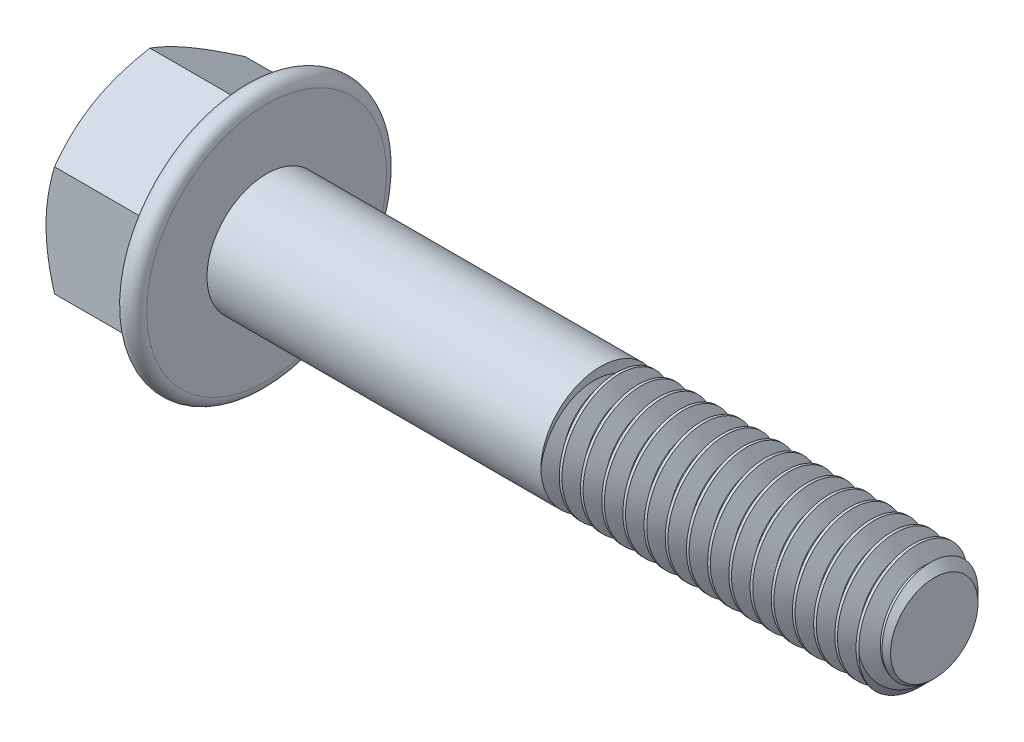
SolidWorks part; units mm, degrees
ref_plane "Front Plane" through (0, 0, 0) normal (0, 0, 1) x (1, 0, 0)
ref_plane "Top Plane" through (0, 0, 0) normal (0, 1, 0) x (1, 0, 0)
ref_plane "Right Plane" through (0, 0, 0) normal (1, 0, 0) x (0, 0, -1)
sketch "Sketch1" plane through (0, 0, 0) normal (0, 0, 1) x (1, 0, 0)
  line L0 (0, 0) -> (44.45, 0) construction
  line L1 (0, 0) -> (-8.3344, 0) construction
  line L2 (0, 8.7312) -> (0, -8.7312) construction
  line L3 (-8.3344, 6.35) -> (-8.3344, -6.35) construction
  line L4 (44.45, 3.9688) -> (44.45, -3.9688) construction
  point P8 (22.225, 0)
  point P11 (39.5111, -3.9688)
  dimension "D1" = 4.9389
sketch "Sketch2" plane through (0, 0, 0) normal (1, 0, 0) x (0, 0, -1)
  circle A0 centre (0, 0) radius 3.9688
extrude "Boss-Extrude1" add sketch "Sketch2" along normal up to vertex (44.45 mm away) up to point (44.45, 3.9688, 0)
chamfer "Chamfer1" distance 1.0583 angle 45 1 edges at (44.45, 0, -3.9688)
sketch "Sketch12" plane through (44.45, 0, 0) normal (1, 0, 0) x (0, 0, -1)
  circle A0 centre (0, 0) radius 3.9688 construction
  circle A1 centre (0, 0) radius 3.9688
curve "Helix/Spiral2" pitch 1.4111 height 45.8611 radius 3.9688 centre (44.45, 0, 0) axis (-1, 0, 0) start towards (0, 1, 0) parameters "Pitch"=1.4111
sketch "Sketch13" plane through (0, 0, 0) normal (0, 0, 1) x (1, 0, 0)
  line L0 (44.45, 3.9688) -> (44.9792, 3.0522)
  line L1 (44.9792, 3.0522) -> (45.1556, 3.0522)
  line L2 (45.1556, 3.0522) -> (45.6847, 3.9688)
  line L3 (45.6847, 3.9688) -> (44.45, 3.9688)
  line L4 (45.0674, 3.9688) -> (45.0674, 3.0522) construction
  line L5 (44.7146, 3.5105) -> (45.4201, 3.5105) construction
  line L6 (44.45, -3.9688) -> (44.45, 3.9688) construction
  dimension "D1" = 60
  dimension "D2" = 0.7056
  dimension "D3" = 0.1764
sweep "Cut-Sweep1" cut profiles "Sketch13" path "Helix/Spiral2" align with end faces yes
ref_plane "Plane1" through (22.225, 0, 0) normal (1, 0, 0) x (0, 0, -1)
sketch "Sketch3" plane through (0, 0, 0) normal (-1, 0, 0) x (0, 0, 1)
  line L0 (0, 7.3323) -> (0, 0) construction
  line L1 (0, 7.3323) -> (-6.35, 3.6662)
  line L2 (-6.35, 3.6662) -> (-6.35, -3.6662)
  line L3 (-6.35, -3.6662) -> (0, -7.3323)
  line L4 (0, -7.3323) -> (6.35, -3.6662)
  line L5 (6.35, -3.6662) -> (6.35, 3.6662)
  line L6 (6.35, 3.6662) -> (0, 7.3323)
  circle A0 centre (0, 0) radius 6.35 construction
extrude "Boss-Extrude2" add sketch "Sketch3" along normal up to vertex (8.3344 mm away) up to point (-8.3344, 6.35, 0)
sketch "Sketch4" plane through (0, 0, 0) normal (0, 0, 1) x (1, 0, 0)
  line L0 (0, 0) -> (0, 7.9869)
  line L1 (-0.7444, 8.7312) -> (0, 8.7312) construction
  line L2 (-1.3891, 8.3591) -> (-2.549, 6.35)
  line L3 (-2.549, 6.35) -> (-2.549, 0)
  line L4 (0, 0) -> (-8.3344, 0) construction
  line L5 (-2.549, 0) -> (0, 0)
  line L6 (-8.3344, 6.35) -> (-2.549, 6.35) construction
  arc A0 (0, 7.9869) -> (-1.3891, 8.3591) centre (-0.7444, 7.9869) ccw
  dimension "D1" = 30
  dimension "D2" = 1.3891
revolve "Revolve1" add sketch "Sketch4" angle 360 about L5
sketch "Sketch5" plane through (-8.3344, 0, 0) normal (-1, 0, 0) x (0, 0, 1)
  circle A0 centre (0, 0) radius 6.35 construction
  circle A1 centre (0, 0) radius 6.35
extrude "Cut-Extrude1" cut sketch "Sketch5" against normal up to vertex (8.3344 mm away) draft 60 flip side to cut up to point (0, 0, 0)
sketch "Sketch6" plane through (-8.3344, 0, 0) normal (-1, 0, 0) x (0, 0, 1)
  line L0 (0, 6.35) -> (0, -6.35) construction
  circle A0 centre (0, 0) radius 5.715
  dimension "D1" = 11.43
extrude "Cut-Extrude2" cut sketch "Sketch6" against normal blind 0.6945 draft 35
sketch "Sketch11" plane through (-7.6398, 0, 0) normal (-1, 0, 0) x (0, 0, 1)
  line L0 (0, 4.8895) -> (0, 1.7145) construction
  line L1 (0.1905, 4.8895) -> (0.1905, 1.7145)
  line L2 (-0.1905, 4.8895) -> (-0.1905, 1.7145)
  arc A0 (0.1905, 4.8895) -> (-0.1905, 4.8895) centre (0, 4.8895) ccw
  arc A1 (-0.1905, 1.7145) -> (0.1905, 1.7145) centre (0, 1.7145) ccw
  circle A2 centre (0, 0) radius 5.08 construction
  circle A3 centre (0, 0) radius 1.524 construction
  point P3 (0, 3.302)
  dimension "D1" = 10.16
  dimension "D2" = 3.048
  dimension "D3" = 0.381
extrude "Cut-Extrude3" cut sketch "Sketch11" against normal blind 0.254
pattern_circular "CirPattern1" count 6 over 360 about axis through (0, 0, 0) along (1, 0, 0) of "Cut-Extrude3"
sketch "Sketch14" plane through (0, 0, 0) normal (0, 0, 1) x (1, 0, 0)
  line L0 (0, 3.9687) -> (0, 0)
  line L1 (0, 0) -> (22.225, 0)
  line L2 (22.225, 0) -> (22.225, 3.9687)
  line L3 (22.225, 3.9687) -> (0, 3.9687)
revolve "Revolve2" add sketch "Sketch14" angle 360 mid plane about L1
equation "\"D2@Sketch4\" = \"Head Ht.@Sketch1\" / 6"
equation "\"D1@Sketch6\" = \"Head Wd.@Sketch1\" * 0.9"
equation "\"D1@Cut-Extrude2\" = \"D2@Sketch4\" / 2"
equation "\"D1@Sketch11\" = \"Head Wd.@Sketch1\"*.8"
equation "\"D2@Sketch11\" = \"D1@Sketch11\"*.3"
equation "\"D3@Sketch11\" = \"Head Wd.@Sketch1\"*.03"
equation "\"D2@Sketch13\" = \"Pitch@Helix/Spiral2\"*.50"
equation "\"D3@Sketch13\" = \"Pitch@Helix/Spiral2\"*.125"
equation "\"D3@Helix/Spiral2\" = \"Lg.@Sketch1\"+\"Pitch@Helix/Spiral2\""
equation "\"D1@Chamfer1\" = \"Pitch@Helix/Spiral2\"*.750"
equation "\"D1@Sketch1\" = \"Pitch@Helix/Spiral2\"*3.50"
